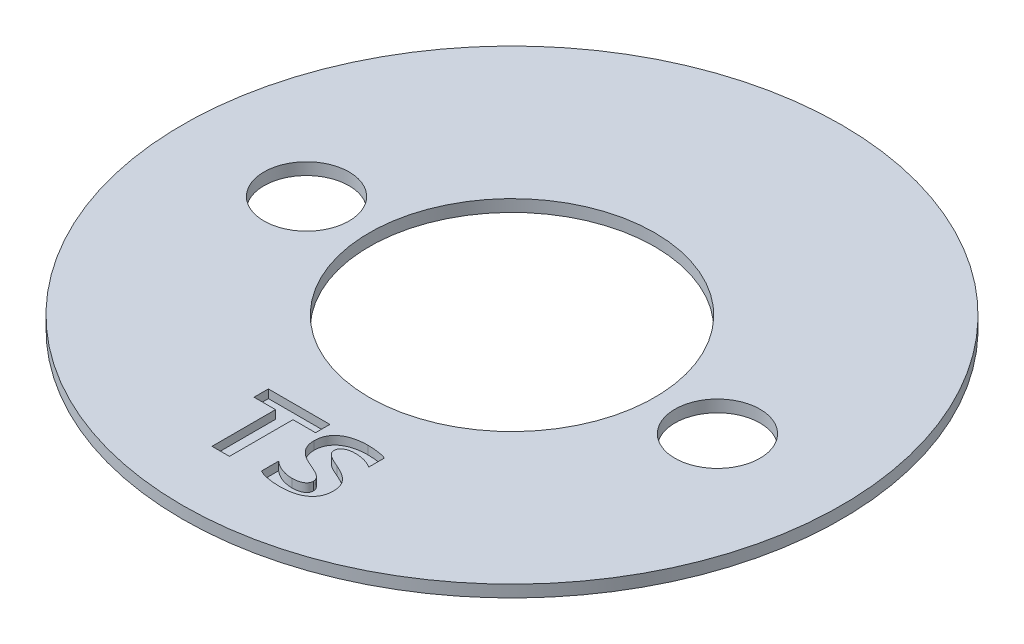
SolidWorks part; units mm, degrees
material "ABS"
ref_plane "Front Plane" through (0, 0, 0) normal (0, 0, 1) x (1, 0, 0)
ref_plane "Top Plane" through (0, 0, 0) normal (0, 1, 0) x (1, 0, 0)
ref_plane "Right Plane" through (0, 0, 0) normal (1, 0, 0) x (0, 0, -1)
sketch "Sketch1" plane through (0, 0, 0) normal (0, 1, 0) x (1, 0, 0)
  circle A0 centre (0, 0) radius 27.5
  dimension "D1" = 55
extrude "Boss-Extrude1" add sketch "Sketch1" along normal blind 1
sketch "Sketch4" plane through (0, 0, 0) normal (0, -1, 0) x (1, 0, 0)
  line L0 (-17.145, 0) -> (17.145, 0) construction
  circle A4 centre (-17.145, 0) radius 3.55
  circle A5 centre (0, 0) radius 11.9062
  circle A6 centre (17.145, 0) radius 3.55
  dimension "D1" = 7.1
  dimension "D2" = 23.8125
  dimension "D3" = 34.29
extrude "Cut-Extrude2" cut sketch "Sketch4" against normal through all
sketch "Sketch2" plane through (0, 1, 0) normal (0, 1, 0) x (1, 0, 0)
  line L0 (-5, -22) -> (5, -22) construction
  line L1 (0, 0) -> (0, -22) construction
  text T0 "TS" font "Nirmala UI" height 6.5
  dimension "D1" = 10
  dimension "D2" = 22
extrude "Cut-Extrude1" cut sketch "Sketch2" against normal offset from surface (0.7 mm away) 0.3 up to face at (-17.145, 0, -3.55)
